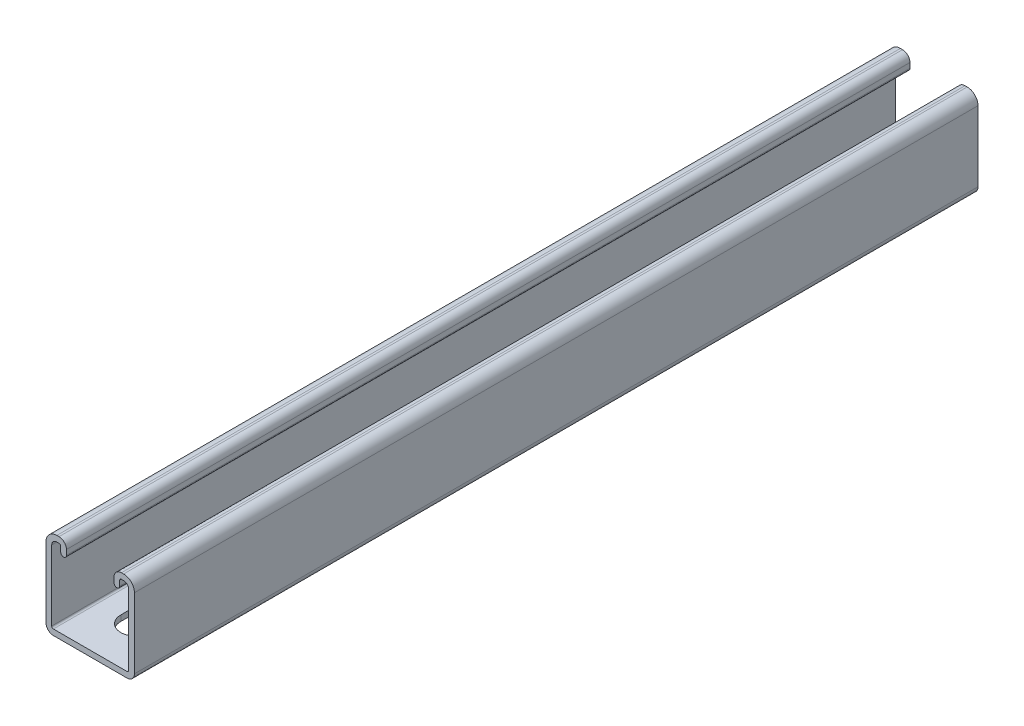
SolidWorks part; units mm, degrees
ref_plane "Front Plane" through (0, 0, 0) normal (0, 0, 1) x (1, 0, 0)
ref_plane "Top Plane" through (0, 0, 0) normal (0, 1, 0) x (1, 0, 0)
ref_plane "Right Plane" through (0, 0, 0) normal (1, 0, 0) x (0, 0, -1)
ref_plane "Plane1" through (0, 0, 3048) normal (0, 0, 1) x (1, 0, 0)
sketch "Sketch1" plane through (0, 0, 0) normal (0, 0, 1) x (1, 0, 0)
  line L0 (-20.6377, 0) -> (-17.9706, 0) construction
  line L1 (20.6377, 0) -> (17.9706, 0) construction
  line L2 (17.1769, -17.9704) -> (-17.1769, -17.9704)
  line L3 (-17.9706, -17.1766) -> (-17.9706, 15.5891)
  line L4 (-15.5894, 17.9704) -> (-14.5734, 17.9704)
  line L5 (-13.7797, 17.1766) -> (-13.7797, 14.8335)
  line L6 (-11.1127, 14.8335) -> (-11.1127, 17.1766)
  line L7 (-14.5734, 20.6374) -> (-15.5894, 20.6374)
  line L8 (-20.6377, 15.5891) -> (-20.6377, -17.1766)
  line L9 (-17.1769, -20.6374) -> (17.1769, -20.6374)
  line L10 (20.6377, 15.5891) -> (20.6377, -17.1766)
  line L11 (14.5734, 20.6374) -> (15.5894, 20.6374)
  line L12 (11.1127, 14.8335) -> (11.1127, 17.1766)
  line L13 (13.7797, 17.1766) -> (13.7797, 14.8335)
  line L14 (0, -17.9704) -> (0, -20.6374) construction
  line L15 (15.5894, 17.9704) -> (14.5734, 17.9704)
  line L16 (17.9706, -17.1766) -> (17.9706, 15.5891)
  arc A0 (-17.1769, -20.6374) -> (-20.6377, -17.1766) centre (-17.1769, -17.1766) cw
  arc A1 (-17.1769, -17.9704) -> (-17.9706, -17.1766) centre (-17.1769, -17.1766) cw
  arc A2 (-17.9706, 15.5891) -> (-15.5894, 17.9704) centre (-15.5894, 15.5891) cw
  arc A3 (-20.6377, 15.5891) -> (-15.5894, 20.6374) centre (-15.5894, 15.5891) cw
  arc A4 (-14.5734, 17.9704) -> (-13.7797, 17.1766) centre (-14.5734, 17.1766) cw
  arc A5 (-14.5734, 20.6374) -> (-11.1127, 17.1766) centre (-14.5734, 17.1766) cw
  arc A6 (-13.7797, 14.8335) -> (-11.1127, 14.8335) centre (-12.4462, 14.8335) ccw
  arc A7 (13.7797, 14.8335) -> (11.1127, 14.8335) centre (12.4462, 14.8335) cw
  arc A8 (14.5734, 20.6374) -> (11.1127, 17.1766) centre (14.5734, 17.1766) ccw
  arc A9 (14.5734, 17.9704) -> (13.7797, 17.1766) centre (14.5734, 17.1766) ccw
  arc A10 (20.6377, 15.5891) -> (15.5894, 20.6374) centre (15.5894, 15.5891) ccw
  arc A11 (17.9706, 15.5891) -> (15.5894, 17.9704) centre (15.5894, 15.5891) ccw
  arc A12 (17.1769, -17.9704) -> (17.9706, -17.1766) centre (17.1769, -17.1766) ccw
  arc A13 (17.1769, -20.6374) -> (20.6377, -17.1766) centre (17.1769, -17.1766) ccw
  dimension "D4" = 3.4608
  dimension "D5" = 5.0483
  dimension "D7" = 3.4608
  dimension "D1" = 34.3538
  dimension "D2" = 41.2748
  dimension "D3" = 2.667
  dimension "D6" = 1.016
  dimension "D8" = 2.3432
extrude "Primary Extrusion" add sketch "Sketch1" against normal blind 393.7
sketch "Sketch58" plane through (0, -20.6374, 0) normal (0, 1, 0) x (-1, 0, 0)
  line L0 (7.1438, -29.3687) -> (7.1438, -21.4313)
  line L1 (-7.1438, -21.4313) -> (-7.1438, -29.3687)
  line L2 (0, 22.7012) -> (0, -22.7012) construction
  line L3 (-7.1438, -25.4) -> (7.1438, -25.4) construction
  line L4 (17.1769, 0) -> (-17.1769, 0) construction
  arc A0 (7.1438, -29.3687) -> (-7.1438, -29.3687) centre (0, -29.3687) cw
  arc A1 (-7.1438, -21.4313) -> (7.1438, -21.4313) centre (0, -21.4313) cw
  point P12 (0, -36.5125)
  point P13 (0, -14.2875)
  point P14 (0, 0)
  dimension "D2" = 22.225
  dimension "D1" = 14.2875
  dimension "D3" = 25.4
extrude "Slot Cut" cut sketch "Sketch58" along normal up to next contours L0 A1 L1 A0
pattern_linear "LPattern1" count 8 spacing 50.8 along (0, 0, -1) of "Slot Cut"
